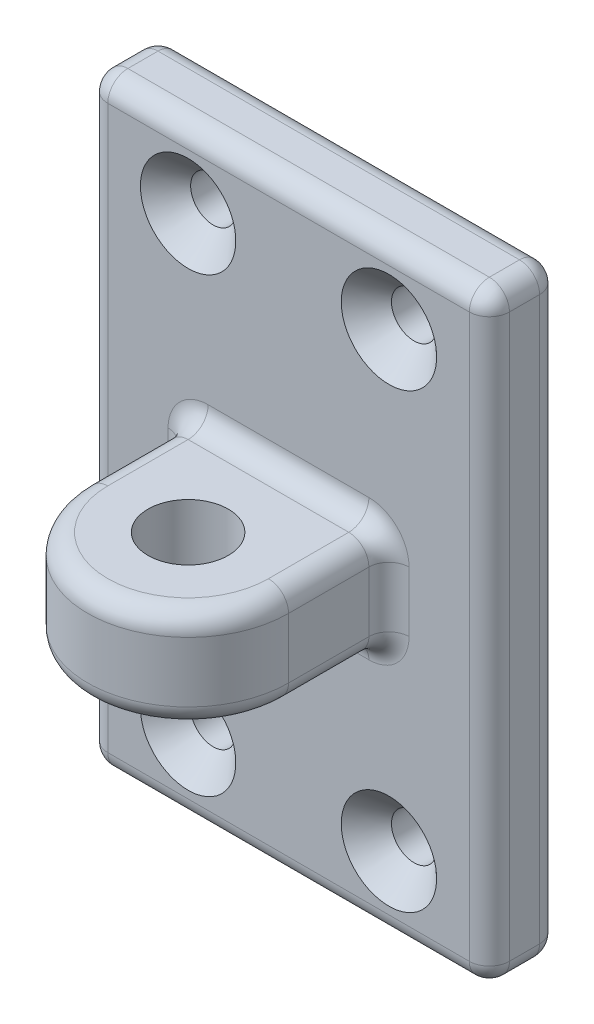
SolidWorks part; units mm, degrees
ref_plane "Plan de face" through (0, 0, 0) normal (0, 0, 1) x (1, 0, 0)
ref_plane "Plan de dessus" through (0, 0, 0) normal (0, 1, 0) x (1, 0, 0)
ref_plane "Plan de droite" through (0, 0, 0) normal (1, 0, 0) x (0, 0, -1)
sketch "Esquisse1" plane through (0, 0, 0) normal (0, 0, 1) x (1, 0, 0)
  line L1 (0, 0) -> (40, 0)
  line L2 (0, 0) -> (0, 60)
  line L3 (0, 60) -> (40, 60)
  line L4 (40, 0) -> (40, 60)
  line L5 (10, 52.5) -> (30, 52.5) construction
  line L6 (10, 52.5) -> (10, 7.5) construction
  line L7 (10, 7.5) -> (30, 7.5) construction
  line L8 (30, 52.5) -> (30, 7.5) construction
  circle A2 centre (10, 52.5) radius 2.25
  circle A3 centre (30, 52.5) radius 2.25
  circle A4 centre (10, 7.5) radius 2.25
  circle A5 centre (30, 7.5) radius 2.25
  point P12 (10, 30)
  point P19 (0, 30)
  point P20 (20, 52.5)
  point P21 (20, 60)
  dimension "D3" = 4.5
  dimension "D1" = 40
  dimension "D2" = 60
  dimension "D4" = 20
  dimension "D5" = 45
extrude "Boss.-Extru.1" add sketch "Esquisse1" along normal blind 7
sketch "Esquisse4" plane through (0, 60, 120) normal (0, 1, 0) x (1, 0, 0)
  line L0 (40, 113) -> (0, 113) construction
  line L1 (30, 113) -> (30, 103)
  line L2 (30, 113) -> (10, 113)
  line L3 (10, 113) -> (10, 103)
  line L4 (30, 103) -> (10, 103) construction
  line L5 (40, 120) -> (0, 120) construction
  arc A0 (30, 103) -> (10, 103) centre (20, 103) cw
  circle A1 centre (20, 103) radius 4
  point P9 (20, 113)
  point P13 (20, 120)
  dimension "D3" = 8
  dimension "D1" = 20
  dimension "D2" = 10
extrude "Boss.-Extru.3" add sketch "Esquisse4" against normal blind 10 from offset 25 offset against normal yes
ref_axis "Axe2" through (20, 25, 17) along (0, 1, 0)
ref_plane "Plan2" through (20, 0, 0) normal (1, 0, 0) x (0, 0, -1)
sketch "Esquisse7" plane through (0, 0, 0) normal (0, 0, -1) x (-1, 0, 0)
  line L0 (-22, 60) -> (-22, 0) construction
  line L1 (-20, 8.25) -> (-20, -8.25) construction
  line L3 (-40, 60) -> (0, 60) construction
  line L6 (0, 0) -> (-40, 0) construction
  text T0 "Minifab" font "Comic Sans MS" height in points 18
  dimension "D1" = 2
extrude "Enlèv. mat.-Extru.1" cut sketch "Esquisse7" against normal blind 0.3
fillet "Congé1" radius 2 22 edges at (20, 35, 7) (10, 30, 7) (30, 30, 7) (10, 25, 12) (30, 25, 12) (10, 35, 12) (30, 35, 12) (20, 25, 27) (20, 35, 27) (20, 60, 7) (20, 60, 0) (40, 30, 7) (40, 60, 3.5) (40, 30, 0) (20, 0, 7) (40, 0, 3.5) (20, 0, 0) (0, 60, 3.5) (0, 30, 7) (0, 0, 3.5) (0, 30, 0) (20, 25, 7)
chamfer "Chanfrein1" distance 2.5 angle 45 4 edges at (32.25, 7.5, 7) (12.25, 7.5, 7) (32.25, 52.5, 7) (12.25, 52.5, 7)
